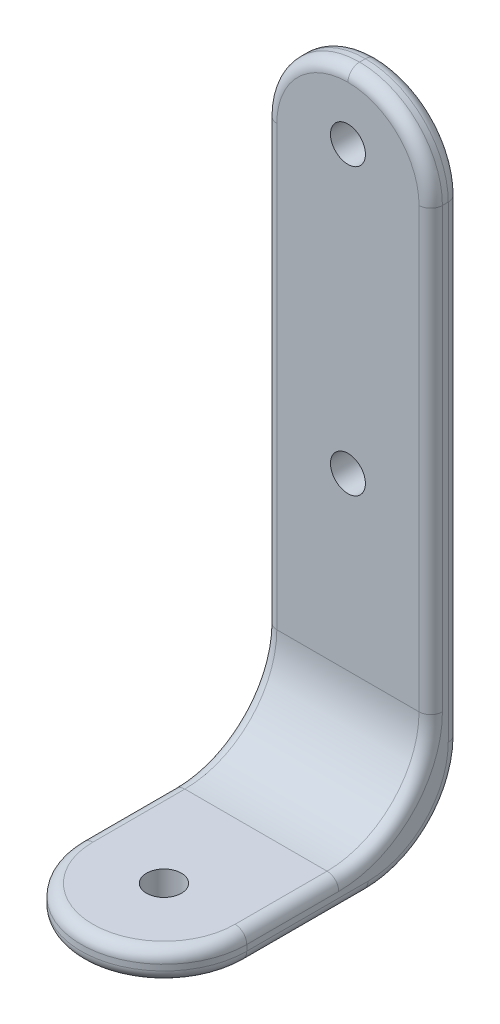
SolidWorks part; units mm, degrees
material "Nickel"
ref_plane "Front Plane" through (0, 0, 0) normal (0, 0, 1) x (1, 0, 0)
ref_plane "Top Plane" through (0, 0, 0) normal (0, 1, 0) x (1, 0, 0)
ref_plane "Right Plane" through (0, 0, 0) normal (1, 0, 0) x (0, 0, -1)
sketch "Sketch1" plane through (0, 0, 0) normal (0, 1, 0) x (1, 0, 0)
  line L0 (-9, 20) -> (-9, 23.175)
  line L1 (-9, 23.175) -> (9, 23.175)
  line L2 (9, 23.175) -> (9, 20)
  line L4 (-9, 0) -> (-9, 20)
  line L5 (-9, 20) -> (9, 20)
  line L6 (9, 0) -> (9, 20)
  arc A0 (-9, 0) -> (9, 0) centre (0, 0) ccw
  dimension "D1" = 18
  dimension "D2" = 3.175
  dimension "D3" = 20
  dimension "D4" = 18
extrude "Base" add sketch "Sketch1" against normal blind 3.175 contours L4 A0 L6 L5 | L0 L5 L2 L1 region at (0, 0, -6.3912) region at (0, 0, -21.5875)
extrude "Riser" add sketch "Sketch1<3>" along normal blind 66.675 contours L0 L5 L2 L1 region at (0, 0, -21.5875)
sketch "Sketch1<3>" plane through (0, 0, 0) normal (0, 1, 0) x (1, 0, 0) same geometry as "Sketch1"
hole_wizard "#6 Clearance Hole2" positions "Sketch3" profile "Sketch2" hole size "#6" standard "Ansi Inch" end condition through all
sketch "Sketch3" plane through (0, 0, 0) normal (0, 1, 0) x (-1, 0, 0)
  point P0 (0, 0)
sketch "Sketch2" plane through (0, 0, 0) normal (1, 0, 0) x (0, 0, 1)
  line L0 (0, 0) -> (0, 3.175)
  line L1 (0, 3.175) -> (1.8986, 3.175)
  line L2 (1.8986, 3.175) -> (1.8986, 0)
  line L5 (1.8986, 0) -> (0, 0)
  line L11 (0, -6.35) -> (0, 107.95) construction
  dimension "Thru Hole Dia." = 3.7973
  dimension "Thru Hole Depth" = 3.175
hole_wizard "#6 Clearance Hole1" positions "Sketch5" profile "Sketch4" hole size "#6" standard "Ansi Inch" end condition through all
sketch "Sketch5" plane through (0, 0, -20) normal (0, 0, 1) x (1, 0, 0)
  line L0 (0, 66.675) -> (0, 59.575) construction
  line L1 (-9, 66.675) -> (9, 66.675) construction
  line L2 (0, 59.575) -> (0, 28.575) construction
  line L3 (0, 28.575) -> (0, 0) construction
  line L4 (-9, 0) -> (9, 0) construction
  point P0 (0, 59.575)
  point P1 (0, 28.575)
  dimension "D1" = 28.575
  dimension "D2" = 31
sketch "Sketch4" plane through (0, 59.575, -20) normal (1, 0, 0) x (0, -1, 0)
  line L0 (0, 0) -> (0, 3.175)
  line L1 (0, 3.175) -> (1.8986, 3.175)
  line L2 (1.8986, 3.175) -> (1.8986, 0)
  line L5 (1.8986, 0) -> (0, 0)
  line L11 (0, -6.35) -> (0, 107.95) construction
  dimension "Thru Hole Dia." = 3.7973
  dimension "Thru Hole Depth" = 3.175
fillet "Fillet1" radius 10 1 edges
fillet "Fillet2" radius 9 2 edges at (-9, 66.675, -21.5875) (9, 66.675, -21.5875)
fillet "Fillet3" radius 10 1 edges at (0, -3.175, -23.175)
fillet "Fillet4" radius 1.27 18 edges at (9, -0.2461, -20.2461) (9, -3.175, -6.5875) (0, -3.175, 9) (-9, -3.175, -6.5875) (-9, -0.2461, -20.2461) (-9, 32.25, -23.175) (-6.364, 64.039, -23.175) (6.364, 64.039, -23.175) (6.364, 64.039, -20) (-6.364, 64.039, -20) (-9, 2.9289, -17.0711) (0, 0, 9) (9, 2.9289, -17.0711) (9, 32.25, -23.175)
